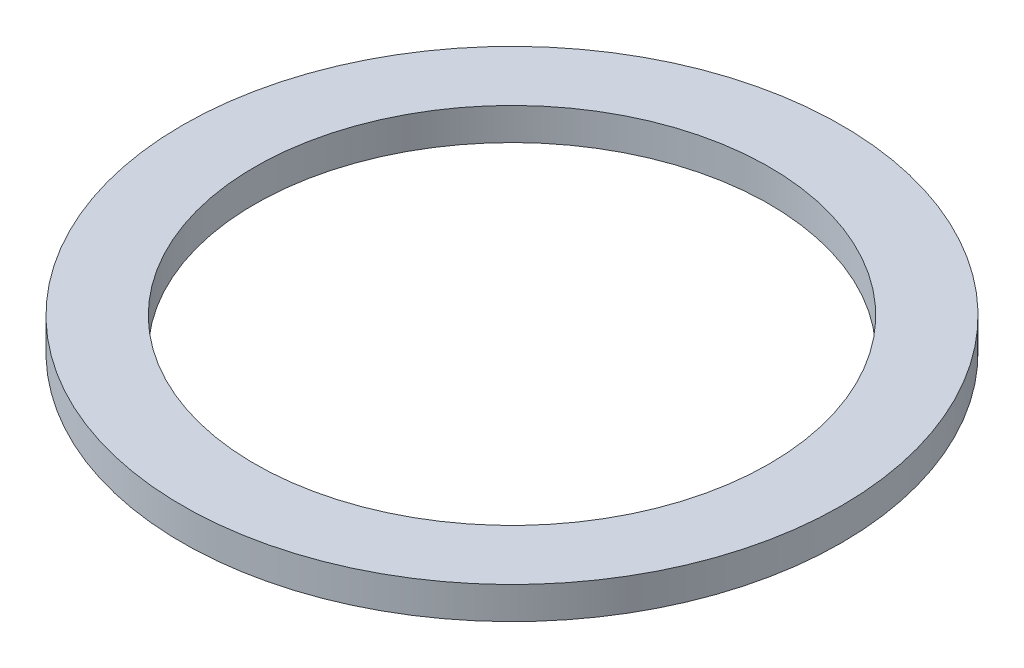
SolidWorks part; units mm, degrees
ref_plane "Front Plane" through (0, 0, 0) normal (0, 0, 1) x (1, 0, 0)
ref_plane "Top Plane" through (0, 0, 0) normal (0, 1, 0) x (1, 0, 0)
ref_plane "Right Plane" through (0, 0, 0) normal (1, 0, 0) x (0, 0, -1)
sketch "Sketch1" plane through (0, 0, 0) normal (0, 0, 1) x (1, 0, 0)
  line L0 (0, -200000) -> (0, 218797.9879) construction
  line L1 (130.175, 154.6921) -> (130.175, 141.9921) construction
  line L2 (101.6, 154.6921) -> (130.175, 154.6921) construction
  line L3 (122.68, 141.9921) -> (101.6, 141.9921) construction
  line L4 (101.6, 141.9921) -> (101.6, 154.6921) construction
  line L5 (0, -200000) -> (0, 218797.9879) construction
  line L6 (130.175, 154.6921) -> (130.175, 141.9921)
  line L7 (101.6, 154.6921) -> (130.175, 154.6921)
  line L8 (130.175, 141.9921) -> (101.6, 141.9921)
  line L9 (101.6, 141.9921) -> (101.6, 154.6921)
  point P7 (148.3548, 141.9921)
revolve "Revolve1" add sketch "Sketch1" angle 360 about L5
